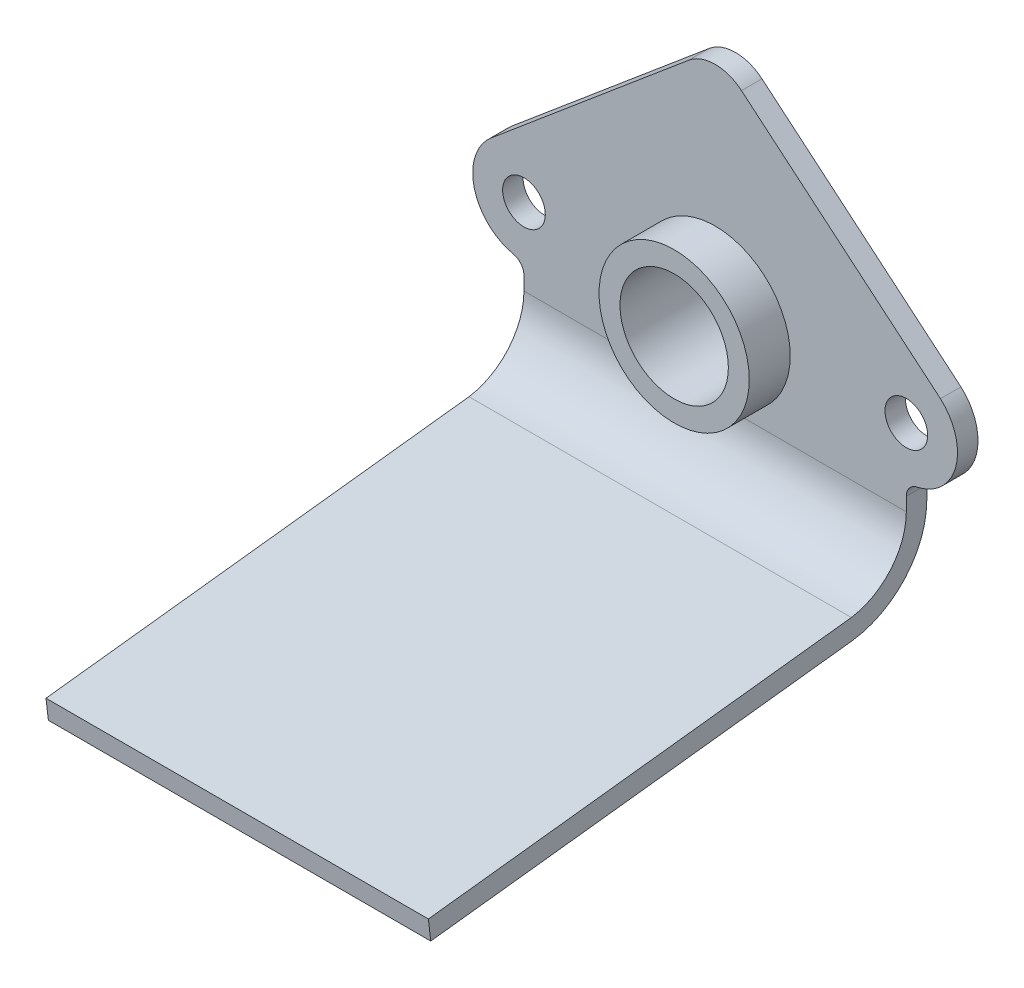
SolidWorks part; units mm, degrees
ref_plane "Front Plane" through (0, 0, 0) normal (0, 0, 1) x (1, 0, 0)
ref_plane "Top Plane" through (0, 0, 0) normal (0, 1, 0) x (1, 0, 0)
ref_plane "Right Plane" through (0, 0, 0) normal (1, 0, 0) x (0, 0, -1)
sketch "Sketch2" plane through (0, 0, 0) normal (0, 0, 1) x (1, 0, 0)
  line L0 (-3.8611, 30.0926) -> (-32.8264, 5.7407)
  line L1 (3.8611, 30.0926) -> (32.9978, 5.5921)
  line L2 (-28, -7.5) -> (-28, -11.25)
  line L3 (28, -7.5) -> (28, -11.25)
  line L4 (-28, -11.25) -> (28, -11.25)
  circle A0 centre (0, 0) radius 7.9375
  circle A1 centre (-28, 0) radius 3.125
  circle A2 centre (28, 0) radius 3.125
  arc A3 (3.8619, 30.0919) -> (-3.8611, 30.0926) centre (0, 25.5) ccw
  arc A4 (-1.3989, -10.9107) -> (0, -11) centre (0, 0) ccw
  arc A5 (-32.8264, 5.7407) -> (-28, -7.5) centre (-28, 0) ccw
  arc A6 (28, -7.5) -> (32.6516, 5.8833) centre (28, 0) ccw
  circle A7 centre (0, 0) radius 7.9375
  circle A8 centre (0, 0) radius 11
  circle A9 centre (0, 0) radius 7.9375
  dimension "D1" = 15.875
  dimension "D4" = 6.25
  dimension "D5" = 6.25
  dimension "D6" = 12
  dimension "D9" = 22
  dimension "D10" = 15
  dimension "D11" = 15
  dimension "D12" = 15.875
  dimension "D13" = 22
  dimension "D2" = 28
  dimension "D3" = 28
  dimension "D7" = 25.5
  dimension "D8" = 28
  dimension "D14" = 11.25
  dimension "D15" = 11.25
extrude "Boss-Extrude2" add sketch "Sketch2" along normal blind 3 contours A8 A6 L1 A3 L0 A5 A4 A1 A2 | A4 A8 A0 region at (0, 30.6712, 0) region at (-7.0612, 8.0244, 0)
sketch "Sketch5" plane through (0, 0, 0) normal (0, 0, -1) x (-1, 0, 0)
  circle A2 centre (0, 0) radius 11
  circle A3 centre (0, 0) radius 7.9375
  dimension "D1" = 15.875
extrude "Boss-Extrude3" add sketch "Sketch5" along normal blind 6 contours A2 | A3
sketch "Sketch6" plane through (0, 0, 3) normal (0, 0, 1) x (1, 0, 0)
  line L0 (-28, -11) -> (28, -11) construction
  circle A0 centre (0, 0) radius 11
  circle A2 centre (0, 0) radius 7.9375
  dimension "D1" = 22
  dimension "D2" = 11
extrude "Boss-Extrude4" add sketch "Sketch6" along normal blind 6
sketch "Sketch8" plane through (-28, 0, 0) normal (-1, 0, 0) x (0, 0, 1)
  line L0 (3, -7.5) -> (3, -11.25) construction
  line L1 (3, -11.25) -> (0, -11.25) construction
  line L2 (73, -27.9) -> (19.4711, -21.6256)
  line L3 (11.7435, -20.7198) -> (11.0461, -20.6381)
  line L4 (3, 30.0926) -> (3, 5.7407) construction
  line L5 (73, -27.9) -> (72.6511, -30.8796)
  line L6 (72.6511, -30.8796) -> (11.0461, -23.6652)
  line L7 (0, -11.25) -> (3, -11.25)
  line L8 (19.4711, -21.6256) -> (11.0461, -20.6381)
  arc A0 (3, -11.25) -> (11.0461, -20.6381) centre (12.5, -11.25) ccw
  arc A1 (0, -11.25) -> (11.0461, -23.6652) centre (12.5, -11.25) ccw
  dimension "D1" = 19
  dimension "D2" = 9.5
  dimension "D3" = 0
  dimension "D4" = 70
  dimension "D5" = 27.9
  dimension "D6" = 3
ref_axis "Axis1" through (0, 0, 9) along (0, 0, -1)
extrude "Boss-Extrude5" add sketch "Sketch8" against normal up to surface (56 mm away) contours A0 L7 A1 L6 L5 L2 L8 up to face at (28, -9.375, 1.5)
fillet "Fillet1" radius 2 2 edges at (28, -7.5, 1.5) (-28, -7.5, 1.5)
